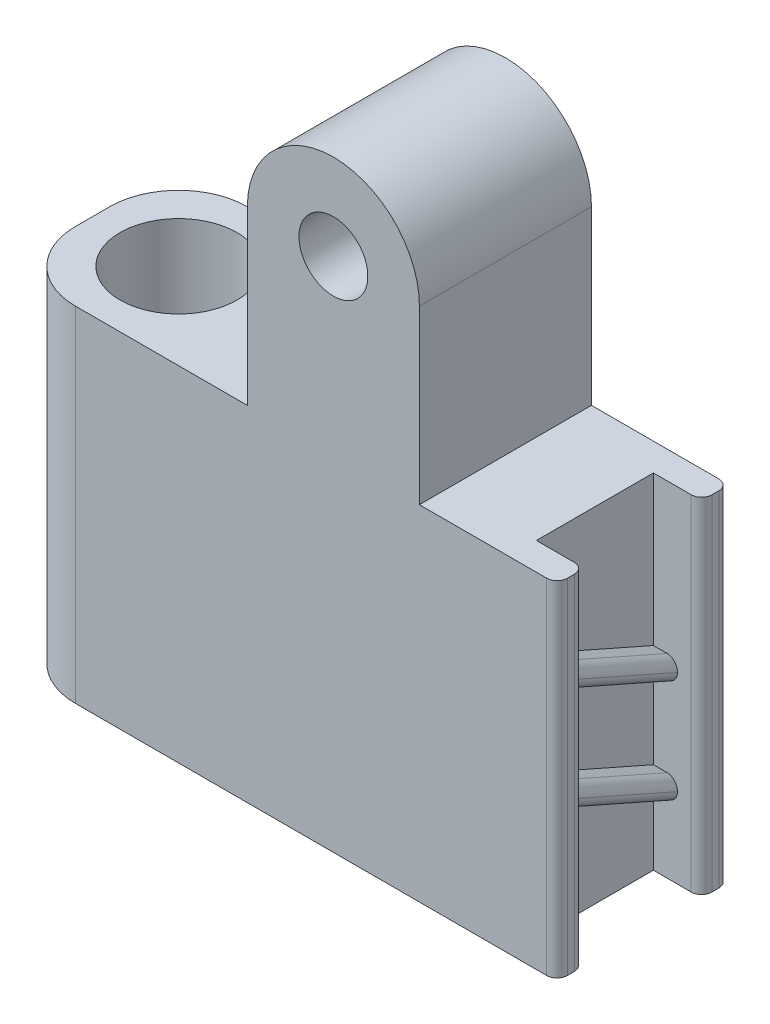
SolidWorks part; units mm, degrees
ref_plane "前基準面" through (0, 0, 0) normal (0, 0, 1) x (1, 0, 0)
ref_plane "上基準面" through (0, 0, 0) normal (0, 1, 0) x (1, 0, 0)
ref_plane "右基準面" through (0, 0, 0) normal (1, 0, 0) x (0, 0, -1)
sketch "草圖1" plane through (0, 0, 0) normal (0, 1, 0) x (1, 0, 0)
  line L0 (13.5, -0.8) -> (11.5, -0.8)
  line L1 (0, 0) -> (13.5, 0)
  line L3 (0, -5) -> (13.5, -5)
  line L4 (13.5, 0) -> (13.5, -0.8)
  line L5 (11.5, -0.8) -> (11.5, -4.2)
  line L6 (11.5, -4.2) -> (13.5, -4.2)
  line L7 (13.5, -4.2) -> (13.5, -5)
  line L9 (0, 0) -> (0, -5) construction
  line L10 (0, 0) -> (-2.5, 0)
  line L11 (-2.5, 0) -> (-2.5, -5)
  line L12 (-2.5, -5) -> (0, -5)
  circle A1 centre (0, -2.5) radius 1.7
  dimension "D2" = 2.5
  dimension "D7" = 3.4
  dimension "D1" = 5
  dimension "D3" = 13.5
  dimension "D4" = 0.8
  dimension "D5" = 0.8
  dimension "D6" = 2
extrude "填料-伸長1" add sketch "草圖1" along normal blind 10
sketch "草圖2" plane through (11.5, 0, 0) normal (1, 0, 0) x (0, 0, -1)
  line L0 (-4.2, 7.1558) -> (-0.8, 5.6558)
  line L1 (-4.2, 10) -> (-4.2, 0) construction
  line L2 (-0.8, 10) -> (-0.8, 0) construction
  line L3 (-0.8, 5.6558) -> (-0.8, 5)
  line L4 (-0.8, 10) -> (-0.8, 0) construction
  line L5 (-0.8, 5) -> (-4.2, 6.5)
  line L6 (-4.2, 6.5) -> (-4.2, 7.1558)
  line L7 (-4.2, 4.1558) -> (-0.8, 2.6558)
  line L8 (-4.2, 10) -> (-4.2, 0) construction
  line L9 (-0.8, 2.6558) -> (-0.8, 2)
  line L10 (-0.8, 2) -> (-4.2, 3.5)
  line L11 (-4.2, 3.5) -> (-4.2, 4.1558)
  dimension "D1" = 0.6
  dimension "D2" = 0.6
  dimension "D3" = 3
  dimension "D4" = 2
  dimension "D5" = 1.5
extrude "填料-伸長2" add sketch "草圖2" along normal blind 1.3
fillet "圓角1" radius 0.3 4 edges at (12.8, 6.4058, 2.5) (12.8, 5.75, 2.5) (12.8, 3.4058, 2.5) (12.8, 2.75, 2.5)
fillet "圓角2" radius 0.3 4 edges at (13.5, 5, 5) (13.5, 5, 0) (13.5, 5, 0.8) (13.5, 5, 4.2)
sketch "草圖3" plane through (0, 0, 0) normal (0, 0, 1) x (1, 0, 0)
  line L0 (4.5, 10) -> (4.5, 15)
  line L1 (-2.5, 10) -> (13.2, 10) construction
  line L2 (-2.5, 10) -> (-2.5, 0) construction
  line L3 (9.5, 15) -> (9.5, 10)
  line L4 (9.5, 10) -> (4.5, 10)
  arc A0 (9.5, 15) -> (4.5, 15) centre (7, 15) ccw
  circle A1 centre (7, 15) radius 1
  dimension "D3" = 5
  dimension "D4" = 2
  dimension "D1" = 5
  dimension "D2" = 9.5
extrude "填料-伸長3" add sketch "草圖3" along normal up to surface (5 mm away) up to face at (5.35, 5, 5)
fillet "圓角3" radius 2 2 edges at (-2.5, 5, 5) (-2.5, 5, 0)
sketch "草圖4" plane through (11.5, 0, 0) normal (1, 0, 0) x (0, 0, -1)
  line L1 (-4.2, 10) -> (-0.8, 10)
  line L2 (-4.2, 10) -> (-4.2, 0)
  line L3 (-4.2, 0) -> (-0.8, 0)
  line L4 (-0.8, 10) -> (-0.8, 0)
extrude "填料-伸長4" add sketch "草圖4" along normal blind 0.6
